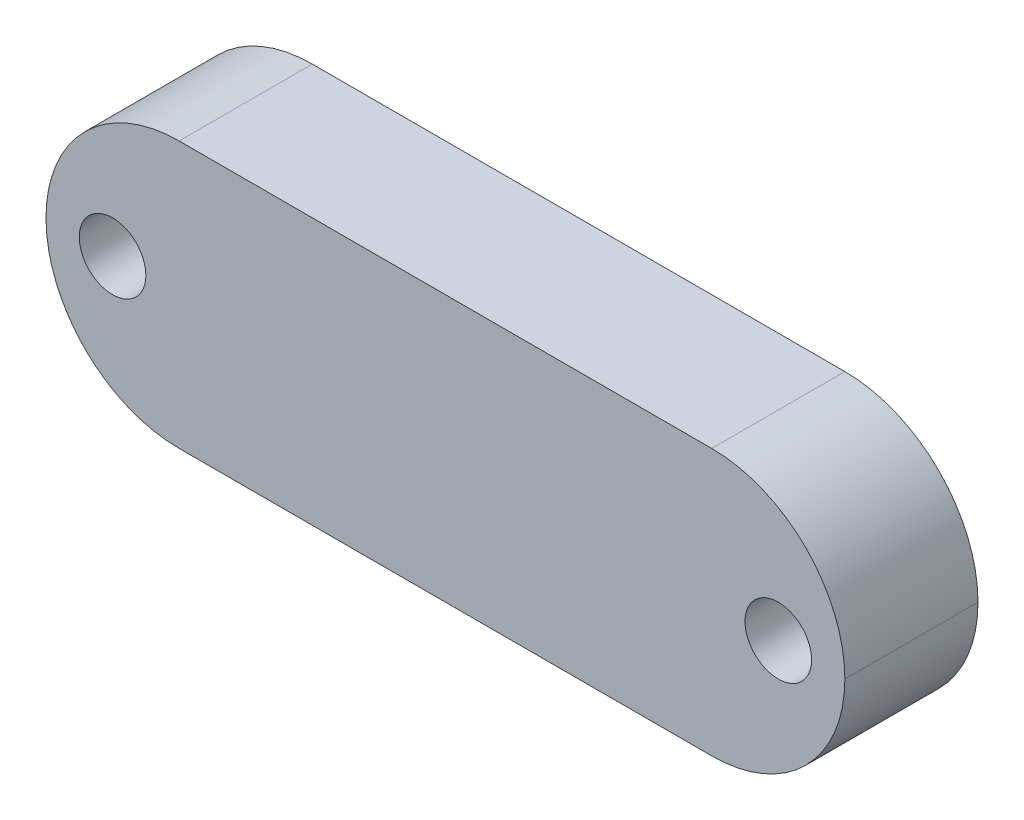
SolidWorks part; units mm, degrees
ref_plane "Front Plane" through (0, 0, 0) normal (0, 0, 1) x (1, 0, 0)
ref_plane "Top Plane" through (0, 0, 0) normal (0, 1, 0) x (1, 0, 0)
ref_plane "Right Plane" through (0, 0, 0) normal (1, 0, 0) x (0, 0, -1)
sketch "Sketch1" plane through (0, 0, 0) normal (0, 0, 1) x (1, 0, 0)
  line L1 (-30, 10) -> (30, 10)
  line L2 (-30, 10) -> (-30, -10)
  line L3 (-30, -10) -> (30, -10)
  line L4 (30, 10) -> (30, -10)
  line L5 (-30, 10) -> (30, -10) construction
  line L6 (-30, -10) -> (30, 10) construction
  circle A0 centre (-25, 0) radius 2.5
  circle A1 centre (25, 0) radius 2.5
  point P0 (0, 0)
  dimension "D4" = 5
  dimension "D5" = 5
  dimension "D6" = 5
  dimension "D1" = 60
  dimension "D2" = 20
  dimension "D3" = 5
extrude "Boss-Extrude1" add sketch "Sketch1" along normal blind 10
fillet "Fillet1" radius 10 4 edges at (30, -10, 5) (30, 10, 5) (-30, -10, 5) (-30, 10, 5)
